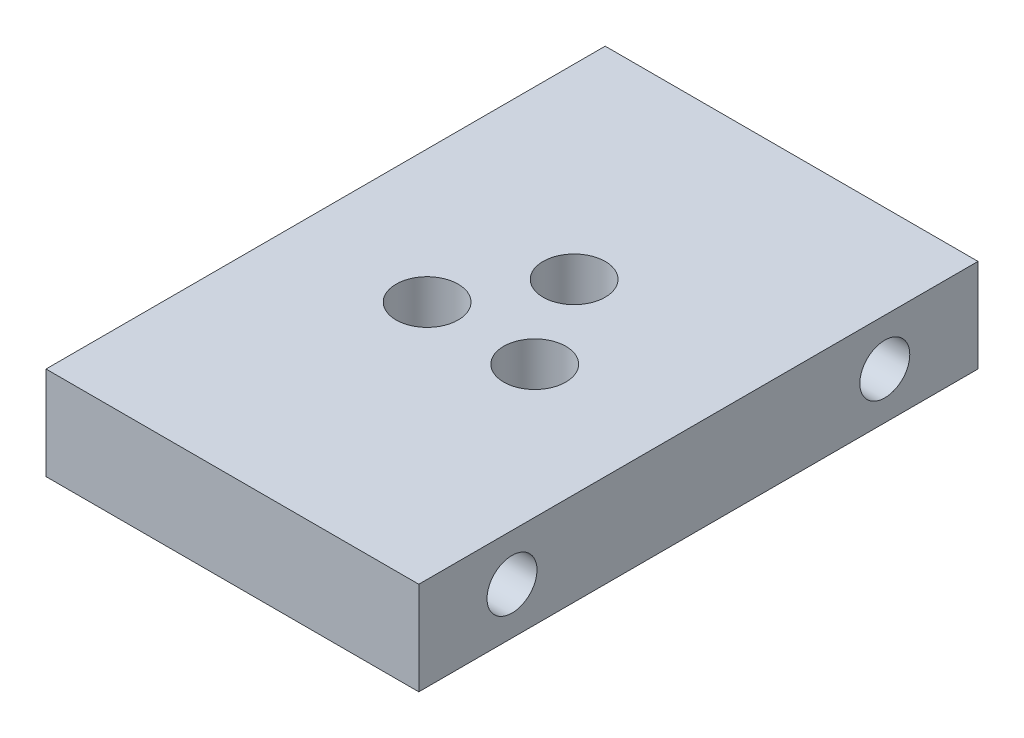
SolidWorks part; units mm, degrees
material "6061 Alloy"
ref_plane "Front Plane" through (0, 0, 0) normal (0, 0, 1) x (1, 0, 0)
ref_plane "Top Plane" through (0, 0, 0) normal (0, 1, 0) x (1, 0, 0)
ref_plane "Right Plane" through (0, 0, 0) normal (1, 0, 0) x (0, 0, -1)
sketch "Sketch1" plane through (0, 0, 0) normal (0, 1, 0) x (1, 0, 0)
  line L1 (-19.05, 28.575) -> (19.05, 28.575)
  line L2 (-19.05, 28.575) -> (-19.05, -28.575)
  line L3 (-19.05, -28.575) -> (19.05, -28.575)
  line L4 (19.05, 28.575) -> (19.05, -28.575)
  line L5 (-19.05, 28.575) -> (19.05, -28.575) construction
  line L6 (-19.05, -28.575) -> (19.05, 28.575) construction
  point P0 (0, 0)
  dimension "D1" = 57.15
  dimension "D2" = 38.1
extrude "Boss-Extrude1" add sketch "Sketch1" along normal blind 9.525
hole_wizard "1/4 (0.25) Diameter Hole1" positions "Sketch3" profile "Sketch2" hole size "1/4" standard "ANSI Inch"
sketch "Sketch3" plane through (0, 0, 0) normal (0, -1, 0) x (-1, 0, 0)
  point P4 (0, 6.35)
  point P21 (5.4993, -3.175)
  point P22 (-5.4993, -3.175)
  dimension "D1" = 6.35
  dimension "D2" = 3
sketch "Sketch2" plane through (0, 0, -6.35) normal (1, 0, 0) x (0, 0, -1)
  line L0 (0, 0) -> (0, 18.9257)
  line L1 (0, 18.9257) -> (3.175, 17.018)
  line L2 (3.175, 17.018) -> (3.175, 0)
  line L5 (3.175, 0) -> (0, 0)
  line L10 (0, 18.9257) -> (-3.175, 17.018) construction
  line L11 (0, -6.35) -> (0, 107.95) construction
  dimension "Hole Dia." = 6.35
  dimension "Hole Depth" = 17.018
  dimension "Drill Angle" = 118
hole_wizard "1/4-20 Tapped Hole1" positions "3DSketch1" profile "Sketch4" tap size "1/4-20" standard "ANSI Inch"
sketch3d "3DSketch1"
  line L4 (19.05, 4.7625, -19.05) -> (19.05, 4.7625, -28.575) construction
  line L5 (19.05, 9.525, -28.575) -> (19.05, 0, -28.575) construction
  line L7 (19.05, 4.7625, 19.05) -> (19.05, 4.7625, 28.575) construction
  line L8 (19.05, 9.525, 28.575) -> (19.05, 0, 28.575) construction
  point P0 (-19.05, 4.7625, -19.05)
  point P2 (-19.05, 4.7625, 19.05)
  point P4 (19.05, 4.7625, 19.05)
  point P6 (19.05, 4.7625, -19.05)
  dimension "D1" = 9.525
sketch "Sketch4" plane through (-19.05, 4.7625, -19.05) normal (0, 1, 0) x (0, 0, 1)
  line L0 (0, 0) -> (0, 18.0438)
  line L1 (0, 18.0438) -> (2.5527, 16.51)
  line L2 (2.5527, 16.51) -> (2.5527, 0)
  line L5 (2.5527, 0) -> (0, 0)
  line L10 (0, 18.0438) -> (-2.5527, 16.51) construction
  line L11 (0, -6.35) -> (0, 107.95) construction
  dimension "Tap Drill Dia." = 5.1054
  dimension "Tap Drill Depth" = 16.51
  dimension "Drill Angle" = 118
